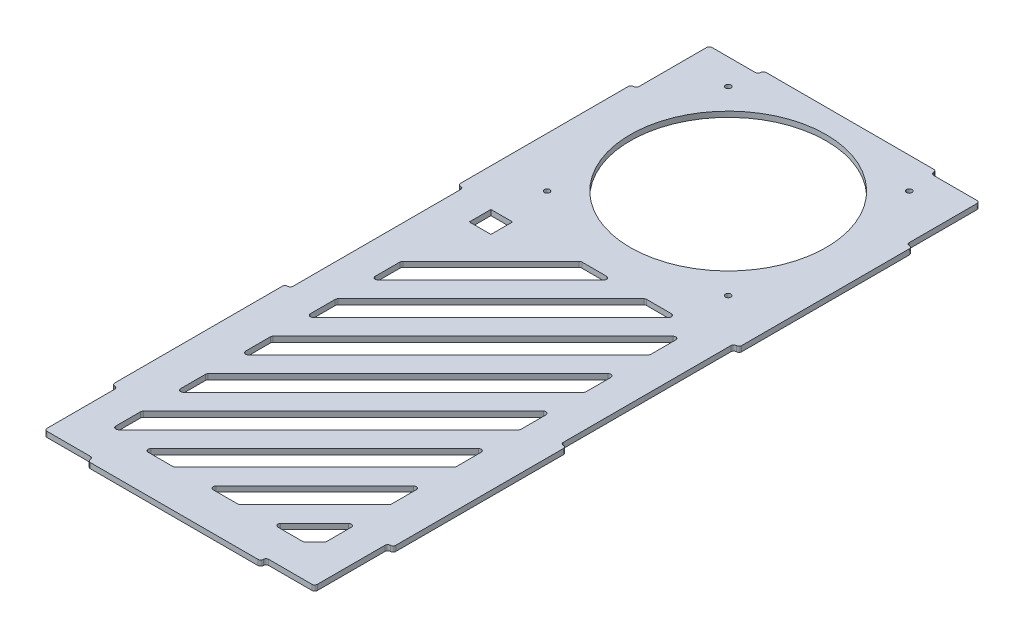
SolidWorks part; units mm, degrees
ref_plane "Front Plane" through (0, 0, 0) normal (0, 0, 1) x (1, 0, 0)
ref_plane "Top Plane" through (0, 0, 0) normal (0, 1, 0) x (1, 0, 0)
ref_plane "Right Plane" through (0, 0, 0) normal (1, 0, 0) x (0, 0, -1)
sketch "Sketch1" plane through (0, 0, 0) normal (0, 1, 0) x (1, 0, 0)
  line L1 (0, 0) -> (158.75, 0)
  line L2 (0, 0) -> (0, 390.525)
  line L3 (0, 390.525) -> (158.75, 390.525)
  line L4 (158.75, 0) -> (158.75, 390.525)
  dimension "D1" = 158.75
  dimension "D2" = 390.525
extrude "Boss-Extrude1" add sketch "Sketch1" along normal blind 3.175
sketch "Sketch2" plane through (0, 0, 0) normal (0, 1, 0) x (1, 0, 0)
  line L0 (158.75, 390.525) -> (0, 390.525) construction
  line L1 (28.575, 393.7) -> (130.175, 393.7)
  line L2 (28.575, 393.7) -> (28.575, 390.525)
  line L3 (28.575, 390.525) -> (130.175, 390.525)
  line L4 (130.175, 393.7) -> (130.175, 390.525)
  line L5 (-55, 0) -> (55, 0) construction
  line L6 (28.575, 0) -> (130.175, 0)
  line L7 (28.575, 0) -> (28.575, -3.175)
  line L8 (28.575, -3.175) -> (130.175, -3.175)
  line L9 (130.175, 0) -> (130.175, -3.175)
  point P12 (79.375, 390.525)
  point P13 (79.375, 390.525)
  dimension "D1" = 101.6
  dimension "D2" = 3.175
  dimension "D3" = 3.175
extrude "Boss-Extrude2" add sketch "Sketch2" along normal blind 3.175
sketch "Sketch3" plane through (0, 0, 0) normal (0, 1, 0) x (1, 0, 0)
  line L0 (0, -55) -> (0, 55) construction
  line L1 (0, 347.6625) -> (-3.175, 347.6625)
  line L2 (0, 347.6625) -> (0, 246.0625)
  line L3 (0, 246.0625) -> (-3.175, 246.0625)
  line L4 (-3.175, 347.6625) -> (-3.175, 246.0625)
  line L5 (158.75, 0) -> (158.75, 390.525) construction
  line L6 (0, 144.4625) -> (-3.175, 144.4625)
  line L7 (0, 144.4625) -> (0, 42.8625)
  line L8 (0, 42.8625) -> (-3.175, 42.8625)
  line L9 (-3.175, 144.4625) -> (-3.175, 42.8625)
  line L10 (158.75, 42.8625) -> (161.925, 42.8625)
  line L11 (158.75, 42.8625) -> (158.75, 144.4625)
  line L12 (158.75, 144.4625) -> (161.925, 144.4625)
  line L13 (161.925, 42.8625) -> (161.925, 144.4625)
  line L14 (-3.175, 144.4625) -> (-3.175, 246.0625) construction
  line L15 (158.75, 246.0625) -> (161.925, 246.0625)
  line L16 (158.75, 246.0625) -> (158.75, 347.6625)
  line L17 (158.75, 347.6625) -> (161.925, 347.6625)
  line L18 (161.925, 246.0625) -> (161.925, 347.6625)
  point P21 (158.75, 195.2625)
  point P22 (-3.175, 195.2625)
  dimension "D1" = 101.6
  dimension "D2" = 101.6
  dimension "D3" = 3.175
extrude "Boss-Extrude3" add sketch "Sketch3" along normal blind 3.175
sketch "Sketch4" plane through (0, 3.175, 0) normal (0, 1, 0) x (1, 0, 0)
  line L0 (130.175, 393.7) -> (28.575, 393.7) construction
  line L1 (19.375, 382.2561) -> (139.375, 382.2561) construction
  line L2 (19.375, 382.2561) -> (19.375, 262.2562) construction
  line L3 (19.375, 262.2562) -> (139.375, 262.2562) construction
  line L4 (139.375, 382.2561) -> (139.375, 262.2562) construction
  line L7 (26.1938, 375.4374) -> (132.5562, 375.4374) construction
  line L8 (26.1938, 375.4374) -> (26.1938, 269.0749) construction
  line L9 (26.1938, 269.0749) -> (132.5563, 269.0749) construction
  line L10 (132.5562, 375.4374) -> (132.5563, 269.0749) construction
  line L11 (130.175, 393.7) -> (28.575, 393.7) construction
  circle A1 centre (26.1938, 375.4374) radius 1.5875
  circle A2 centre (132.5562, 375.4374) radius 1.5875
  circle A3 centre (26.1938, 269.0749) radius 1.5875
  circle A4 centre (132.5563, 269.0749) radius 1.5875
  circle A5 centre (79.375, 322.2561) radius 57.5
  point P6 (79.375, 393.7)
  point P7 (79.375, 382.2561)
  point P8 (79.375, 248.225)
  point P9 (79.375, 375.4374)
  point P10 (132.5562, 322.2561)
  point P11 (139.375, 322.2561)
  dimension "D3" = 3.175
  dimension "D8" = 115
  dimension "D1" = 120
  dimension "D2" = 120
  dimension "D4" = 106.3625
  dimension "D5" = 18.2626
extrude "Cut-Extrude1" cut sketch "Sketch4" against normal through all
sketch "Sketch5" plane through (0, 3.175, 0) normal (0, 1, 0) x (1, 0, 0)
  line L5 (0, 0) -> (28.575, 0) construction
  line L7 (12.7, 249.5562) -> (146.05, 249.5562) construction
  line L12 (12.7, 249.5562) -> (12.7, 12.7) construction
  line L13 (12.7, 12.7) -> (146.05, 12.7) construction
  line L14 (146.05, 249.5562) -> (146.05, 12.7) construction
  line L15 (19.375, 262.2562) -> (139.375, 262.2562) construction
  line L16 (28.575, -3.175) -> (130.175, -3.175) construction
  line L17 (19.05, 243.2062) -> (19.05, 19.05)
  line L18 (19.05, 19.05) -> (139.7, 19.05)
  line L19 (139.7, 243.2062) -> (139.7, 19.05)
  line L20 (19.05, 243.2062) -> (139.7, 243.2062)
  line L21 (19.05, 19.05) -> (139.7, 139.7)
  line L22 (19.05, 38.1) -> (139.7, 158.75)
  line L23 (19.05, 57.15) -> (139.7, 177.8)
  line L24 (19.05, 76.2) -> (139.7, 196.85)
  line L25 (19.05, 95.25) -> (139.7, 215.9)
  line L26 (19.05, 114.3) -> (139.7, 234.95)
  line L27 (19.05, 133.35) -> (139.7, 254)
  line L28 (19.05, 152.4) -> (139.7, 273.05)
  line L29 (19.05, 171.45) -> (139.7, 292.1)
  line L30 (19.05, 190.5) -> (139.7, 311.15)
  line L31 (19.05, 209.55) -> (139.7, 330.2)
  line L32 (19.05, 0) -> (139.7, 120.65)
  line L33 (19.05, -19.05) -> (139.7, 101.6)
  line L34 (19.05, -38.1) -> (139.7, 82.55)
  line L35 (19.05, -57.15) -> (139.7, 63.5)
  line L36 (19.05, -76.2) -> (139.7, 44.45)
  line L37 (19.05, -95.25) -> (139.7, 25.4)
  line L38 (19.05, 228.6) -> (139.7, 349.25)
  point P10 (79.375, -3.175)
  point P11 (79.375, 12.7)
  dimension "D1" = 12.7
  dimension "D2" = 12.7
  dimension "D3" = 133.35
  dimension "D4" = 6.35
  dimension "D5" = 45
  dimension "D6" = 11
extrude "Cut-Extrude2" cut sketch "Sketch5" against normal through all contours L18 L37 L19 L36 | L18 L35 L19 L34 | L18 L33 L19 L32 | L22 L17 L21 L19 | L24 L17 L23 L19 | L26 L17 L25 L19 L20 | L28 L17 L27 L20 | L30 L17 L29 L20 region at (50.4086, 3.175, -211.8476) region at (69.3663, 3.175, -192.8899) region at (79.375, 3.175, -165.1) region at (79.375, 3.175, -127) region at (79.375, 3.175, -88.9) region at (93.4983, 3.175, -65.2517) region at (112.4324, 3.175, -46.3176) region at (130.81, 3.175, -27.94)
fillet "Fillet1" radius 1.5875 28 edges at (0, 1.5875, -347.6625) (-3.175, 1.5875, -347.6625) (-3.175, 1.5875, -246.0625) (0, 1.5875, -246.0625) (0, 1.5875, -144.4625) (-3.175, 1.5875, -144.4625) (-3.175, 1.5875, -42.8625) (0, 1.5875, -42.8625) (0, 1.5875, 0) (28.575, 1.5875, 0) (28.575, 1.5875, 3.175) (130.175, 1.5875, 3.175) (130.175, 1.5875, 0) (158.75, 1.5875, 0) (161.925, 1.5875, -42.8625) (158.75, 1.5875, -42.8625) (161.925, 1.5875, -144.4625) (158.75, 1.5875, -144.4625) (158.75, 1.5875, -246.0625) (161.925, 1.5875, -246.0625) (161.925, 1.5875, -347.6625) (158.75, 1.5875, -347.6625) (158.75, 1.5875, -390.525) (130.175, 1.5875, -390.525) (130.175, 1.5875, -393.7) (28.575, 1.5875, -393.7) (28.575, 1.5875, -390.525) (0, 1.5875, -390.525)
fillet "Fillet2" radius 1.5875 32 edges at (19.05, 1.5875, -76.2) (19.05, 1.5875, -57.15) (19.05, 1.5875, -38.1) (19.05, 1.5875, -19.05) (38.1, 1.5875, -19.05) (57.15, 1.5875, -19.05) (76.2, 1.5875, -19.05) (95.25, 1.5875, -19.05) (114.3, 1.5875, -19.05) (133.35, 1.5875, -19.05) (139.7, 1.5875, -25.4) (139.7, 1.5875, -44.45) (139.7, 1.5875, -63.5) (139.7, 1.5875, -82.55) (139.7, 1.5875, -101.6) (139.7, 1.5875, -120.65) (139.7, 1.5875, -139.7) (139.7, 1.5875, -158.75) (139.7, 1.5875, -177.8) (139.7, 1.5875, -196.85) (139.7, 1.5875, -215.9) (19.05, 1.5875, -95.25) (19.05, 1.5875, -114.3) (19.05, 1.5875, -133.35) (19.05, 1.5875, -152.4) (19.05, 1.5875, -171.45) (109.8561, 1.5875, -243.2062) (128.9061, 1.5875, -243.2062) (90.8061, 1.5875, -243.2062) (71.7561, 1.5875, -243.2062) (19.05, 1.5875, -190.5) (139.7, 1.5875, -234.95)
sketch "Sketch6" plane through (0, 3.175, 0) normal (0, 1, 0) x (1, 0, 0)
  line L0 (0, 0) -> (12.7, 0)
  line L1 (-1.7463, 0) -> (1.7463, 0) construction
  line L2 (146.05, 0) -> (158.75, 0)
  line L3 (131.7625, 0) -> (157.1625, 0) construction
  line L4 (158.75, 1.5875) -> (158.75, 41.275) construction
  line L5 (0, 19.05) -> (12.7, 19.05)
  line L6 (146.05, 19.05) -> (158.75, 19.05)
  line L7 (0, 38.1) -> (12.7, 38.1)
  line L8 (146.05, 38.1) -> (158.75, 38.1)
  line L9 (0, 57.15) -> (12.7, 57.15)
  line L10 (146.05, 57.15) -> (158.75, 57.15)
  line L11 (0, 76.2) -> (12.7, 76.2)
  line L12 (146.05, 76.2) -> (158.75, 76.2)
  line L13 (0, 95.25) -> (12.7, 95.25)
  line L14 (146.05, 95.25) -> (158.75, 95.25)
  line L15 (0, 114.3) -> (12.7, 114.3)
  line L16 (146.05, 114.3) -> (158.75, 114.3)
  line L17 (0, 133.35) -> (12.7, 133.35)
  line L18 (146.05, 133.35) -> (158.75, 133.35)
  line L19 (0, 152.4) -> (12.7, 152.4)
  line L20 (146.05, 152.4) -> (158.75, 152.4)
  line L21 (0, 171.45) -> (12.7, 171.45)
  line L22 (146.05, 171.45) -> (158.75, 171.45)
  line L23 (0, 190.5) -> (12.7, 190.5)
  line L24 (146.05, 190.5) -> (158.75, 190.5)
  line L25 (0, 209.55) -> (12.7, 209.55)
  line L26 (146.05, 209.55) -> (158.75, 209.55)
  line L27 (0, 228.6) -> (12.7, 228.6)
  line L28 (146.05, 228.6) -> (158.75, 228.6)
  line L29 (0, 247.65) -> (12.7, 247.65)
  line L30 (146.05, 247.65) -> (158.75, 247.65)
  line L31 (0, 266.7) -> (12.7, 266.7)
  line L32 (146.05, 266.7) -> (158.75, 266.7)
  line L33 (0, 285.75) -> (12.7, 285.75)
  line L34 (146.05, 285.75) -> (158.75, 285.75)
  line L35 (0, 304.8) -> (12.7, 304.8)
  line L36 (146.05, 304.8) -> (158.75, 304.8)
  line L37 (0, 323.85) -> (12.7, 323.85)
  line L38 (146.05, 323.85) -> (158.75, 323.85)
  line L39 (0, 342.9) -> (12.7, 342.9)
  line L40 (146.05, 342.9) -> (158.75, 342.9)
  line L41 (0, 361.95) -> (12.7, 361.95)
  line L42 (146.05, 361.95) -> (158.75, 361.95)
  line L43 (0, 381) -> (12.7, 381)
  line L44 (146.05, 381) -> (158.75, 381)
  dimension "D1" = 12.7
  dimension "D2" = 12.7
sketch "Sketch7" plane through (0, 3.175, 0) normal (0, 1, 0) x (1, 0, 0)
  line L1 (19.05, 243.2062) -> (31.75, 243.2062)
  line L2 (19.05, 243.2062) -> (19.05, 230.5062)
  line L3 (19.05, 230.5062) -> (31.75, 230.5062)
  line L4 (31.75, 243.2062) -> (31.75, 230.5062)
  line L6 (72.4137, 243.2062) -> (86.9736, 243.2062) construction
  point P4 (19.05, 236.8562)
  dimension "D1" = 12.7
  dimension "D2" = 12.7
  dimension "D3" = 6.35
extrude "Cut-Extrude3" cut sketch "Sketch7" against normal through all
